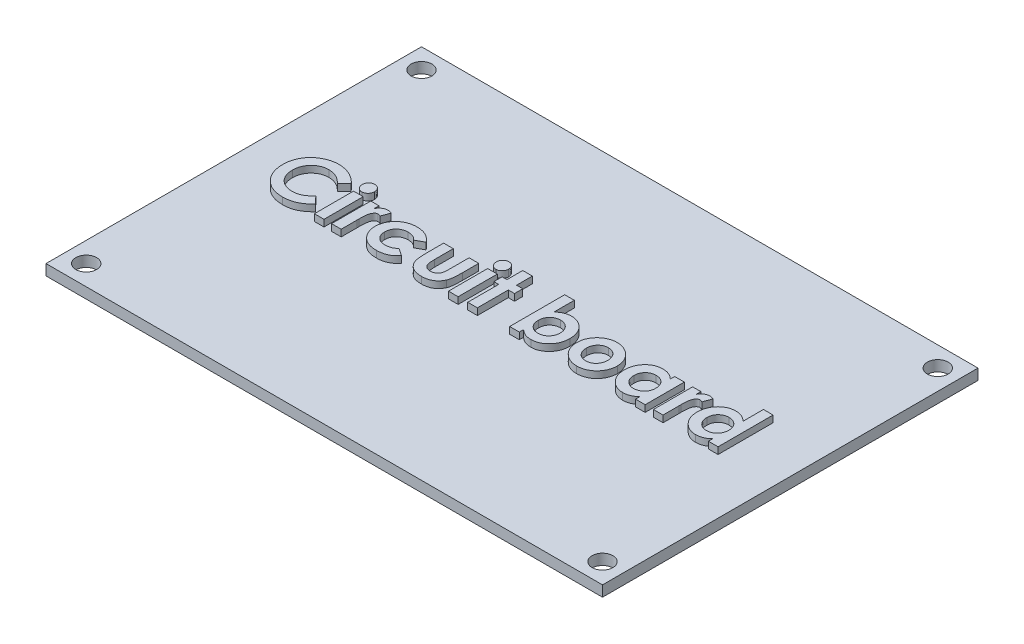
SolidWorks part; units mm, degrees
ref_plane "正面" through (0, 0, 0) normal (0, 0, 1) x (1, 0, 0)
ref_plane "平面" through (0, 0, 0) normal (0, 1, 0) x (1, 0, 0)
ref_plane "右側面" through (0, 0, 0) normal (1, 0, 0) x (0, 0, -1)
sketch "ｽｹｯﾁ1" plane through (0, 0, 0) normal (0, 1, 0) x (1, 0, 0)
  line L0 (-41.5, 28) -> (41.5, 28)
  line L1 (-38.5, 25) -> (38.5, 25) construction
  line L2 (-38.5, 25) -> (-38.5, -25) construction
  line L3 (-38.5, -25) -> (38.5, -25) construction
  line L4 (38.5, 25) -> (38.5, -25) construction
  line L5 (-38.5, 25) -> (38.5, -25) construction
  line L6 (-38.5, -25) -> (38.5, 25) construction
  line L7 (41.5, 28) -> (41.5, -28)
  line L8 (-41.5, -28) -> (41.5, -28)
  line L9 (-41.5, 28) -> (-41.5, -28)
  circle A0 centre (-38.5, 25) radius 1.55
  circle A1 centre (38.5, 25) radius 1.55
  circle A2 centre (38.5, -25) radius 1.55
  circle A3 centre (-38.5, -25) radius 1.55
  point P0 (0, 0)
  dimension "D3" = 3.1
  dimension "D1" = 77
  dimension "D2" = 50
  dimension "D4" = 3
extrude "ﾎﾞｽ - 押し出し1" add sketch "ｽｹｯﾁ1" along normal blind 1.6
sketch "ｽｹｯﾁ2" plane through (0, 1.6, 0) normal (0, 1, 0) x (1, 0, 0)
  text T0 "<b>Circuit board</b>" font "Century Gothic" height 8
extrude "ﾎﾞｽ - 押し出し2" add sketch "ｽｹｯﾁ2" along normal blind 1
